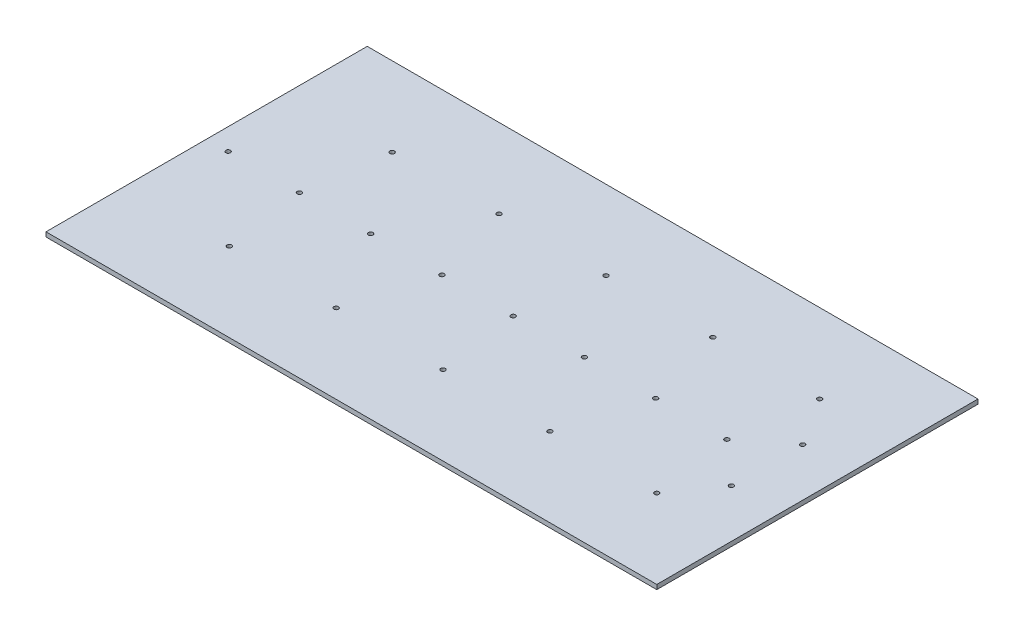
SolidWorks part; units mm, degrees
ref_plane "Front Plane" through (0, 0, 0) normal (0, 0, 1) x (1, 0, 0)
ref_plane "Top Plane" through (0, 0, 0) normal (0, 1, 0) x (1, 0, 0)
ref_plane "Right Plane" through (0, 0, 0) normal (1, 0, 0) x (0, 0, -1)
sketch "Sketch1" plane through (0, 0, 0) normal (0, 1, 0) x (1, 0, 0)
  line L1 (0, 0) -> (857.25, 0)
  line L2 (0, 0) -> (0, 450.85)
  line L3 (0, 450.85) -> (857.25, 450.85)
  line L4 (857.25, 0) -> (857.25, 450.85)
  dimension "D1" = 450.85
  dimension "D2" = 857.25
extrude "Boss-Extrude1" add sketch "Sketch1" along normal blind 6.35
sketch "Sketch2" plane through (0, 6.35, 0) normal (0, 1, 0) x (1, 0, 0)
  line L0 (30.25, 225.425) -> (0, 225.425) construction
  line L1 (0, 450.85) -> (0, 0) construction
  line L2 (730.25, 225.425) -> (857.25, 225.425) construction
  line L3 (30.25, 225.425) -> (130.25, 225.425) construction
  line L4 (146.163, 339.725) -> (0, 339.725) construction
  line L5 (857.25, 0) -> (857.25, 450.85) construction
  line L6 (130.25, 225.425) -> (230.25, 225.425) construction
  line L7 (230.25, 225.425) -> (330.25, 225.425) construction
  line L8 (330.25, 225.425) -> (430.25, 225.425) construction
  line L9 (430.25, 225.425) -> (530.25, 225.425) construction
  line L10 (530.25, 225.425) -> (630.25, 225.425) construction
  line L11 (630.25, 225.425) -> (730.25, 225.425) construction
  line L12 (146.163, 339.725) -> (296.163, 339.725) construction
  line L13 (296.163, 339.725) -> (446.163, 339.725) construction
  line L14 (446.163, 339.725) -> (596.163, 339.725) construction
  line L15 (596.163, 339.725) -> (746.163, 339.725) construction
  line L16 (746.163, 339.725) -> (857.25, 339.725) construction
  line L17 (146.163, 111.125) -> (0, 111.125) construction
  line L18 (146.163, 111.125) -> (296.163, 111.125) construction
  line L20 (296.163, 111.125) -> (446.163, 111.125) construction
  line L21 (446.163, 111.125) -> (596.163, 111.125) construction
  line L22 (596.163, 111.125) -> (746.163, 111.125) construction
  line L23 (746.163, 111.125) -> (857.25, 111.125) construction
  line L24 (789.663, 172.3238) -> (789.663, 111.125) construction
  line L25 (789.663, 172.3238) -> (789.663, 272.3236) construction
  line L26 (0, 0) -> (857.25, 0) construction
  circle A0 centre (30.25, 225.425) radius 3.175
  circle A2 centre (130.25, 225.425) radius 3.175
  circle A3 centre (230.25, 225.425) radius 3.175
  circle A4 centre (330.25, 225.425) radius 3.175
  circle A5 centre (430.25, 225.425) radius 3.175
  circle A6 centre (530.25, 225.425) radius 3.175
  circle A7 centre (630.25, 225.425) radius 3.175
  circle A8 centre (730.25, 225.425) radius 3.175
  circle A11 centre (146.163, 339.725) radius 3.175
  circle A12 centre (296.163, 339.725) radius 3.175
  circle A13 centre (446.163, 339.725) radius 3.175
  circle A14 centre (596.163, 339.725) radius 3.175
  circle A15 centre (746.163, 339.725) radius 3.175
  circle A16 centre (146.163, 111.125) radius 3.175
  circle A17 centre (296.163, 111.125) radius 3.175
  circle A18 centre (446.163, 111.125) radius 3.175
  circle A19 centre (596.163, 111.125) radius 3.175
  circle A20 centre (746.163, 111.125) radius 3.175
  circle A21 centre (789.663, 172.3238) radius 3.175
  circle A22 centre (789.663, 272.3236) radius 3.175
  point P54 (296.163, 110.4225)
  point P55 (296.163, 111.0386)
  dimension "D1" = 6.35
  dimension "D4" = 150
  dimension "D11" = 43.5
  dimension "D2" = 100
  dimension "D3" = 114.3
  dimension "D5" = 111.087
  dimension "D6" = 114.3
  dimension "D7" = 150
  dimension "D8" = 127
  dimension "D9" = 61.1988
  dimension "D10" = 99.9998
  dimension "D12" = 225.425
extrude "Cut-Extrude1" cut sketch "Sketch2" against normal through all both and the other way through all
